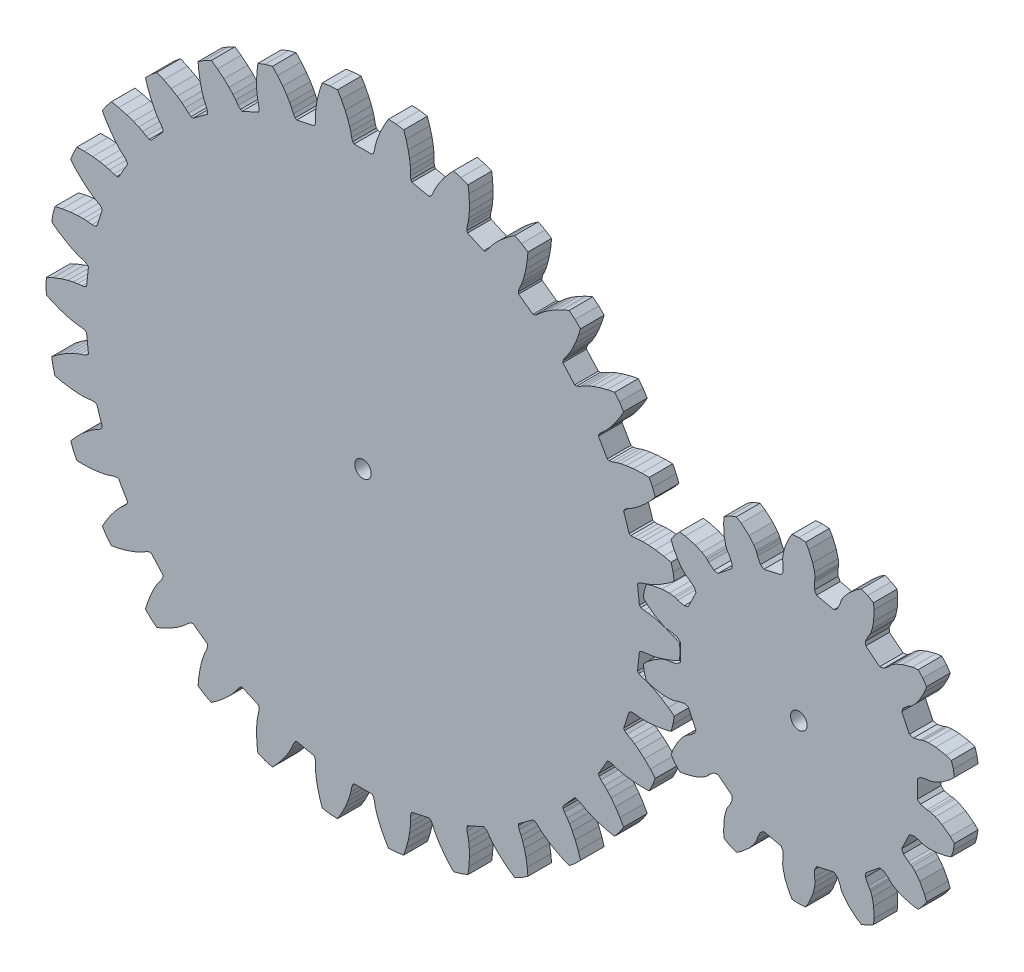
SolidWorks part; units mm, degrees
material "Corrugated Paper"
ref_plane "Front Plane" through (0, 0, 0) normal (0, 0, 1) x (1, 0, 0)
ref_plane "Top Plane" through (0, 0, 0) normal (0, 1, 0) x (1, 0, 0)
ref_plane "Right Plane" through (0, 0, 0) normal (1, 0, 0) x (0, 0, -1)
sketch "Model" plane through (0, 0, 0) normal (0, 0, 1) x (1, 0, 0)
  line L0 (40.3954, -9.6119) -> (40.6554, -8.6416)
  line L1 (40.6554, -8.6416) -> (40.8125, -7.6494)
  line L2 (40.8125, -7.6494) -> (40.0298, -7.0621)
  line L3 (40.0298, -7.0621) -> (39.103, -6.463)
  line L4 (39.103, -6.463) -> (38.2941, -6.0168)
  line L5 (38.2941, -6.0168) -> (37.6191, -5.7037)
  line L6 (37.6191, -5.7037) -> (37.0918, -5.5025)
  line L7 (37.0918, -5.5025) -> (36.5255, -5.3307)
  line L8 (36.5255, -5.3307) -> (36.1596, -5.1469)
  line L9 (36.1596, -5.1469) -> (35.9968, -4.9513)
  line L10 (35.9968, -4.9513) -> (36.2396, -2.6411)
  line L11 (36.2396, -2.6411) -> (36.4395, -2.4836)
  line L12 (36.4395, -2.4836) -> (36.8356, -2.3799)
  line L13 (36.8356, -2.3799) -> (37.4253, -2.3295)
  line L14 (37.4253, -2.3295) -> (37.9829, -2.2424)
  line L15 (37.9829, -2.2424) -> (38.7082, -2.0765)
  line L16 (38.7082, -2.0765) -> (39.5923, -1.8082)
  line L17 (39.5923, -1.8082) -> (40.6234, -1.4149)
  line L18 (40.6234, -1.4149) -> (41.5111, -1.0032)
  line L19 (41.5111, -1.0032) -> (41.5636, 0)
  line L20 (41.5636, 0) -> (41.5111, 1.0032)
  line L21 (41.5111, 1.0032) -> (40.6234, 1.4149)
  line L22 (40.6234, 1.4149) -> (39.5923, 1.8082)
  line L23 (39.5923, 1.8082) -> (38.7082, 2.0765)
  line L24 (38.7082, 2.0765) -> (37.9829, 2.2424)
  line L25 (37.9829, 2.2424) -> (37.4253, 2.3295)
  line L26 (37.4253, 2.3295) -> (36.8356, 2.3799)
  line L27 (36.8356, 2.3799) -> (36.4395, 2.4836)
  line L28 (36.4395, 2.4836) -> (36.2396, 2.6411)
  line L29 (36.2396, 2.6411) -> (35.9968, 4.9513)
  line L30 (35.9968, 4.9513) -> (36.1596, 5.1469)
  line L31 (36.1596, 5.1469) -> (36.5255, 5.3307)
  line L32 (36.5255, 5.3307) -> (37.0918, 5.5025)
  line L33 (37.0918, 5.5025) -> (37.6191, 5.7037)
  line L34 (37.6191, 5.7037) -> (38.2941, 6.0168)
  line L35 (38.2941, 6.0168) -> (39.103, 6.463)
  line L36 (39.103, 6.463) -> (40.0298, 7.0621)
  line L37 (40.0298, 7.0621) -> (40.8125, 7.6494)
  line L38 (40.8125, 7.6494) -> (40.6554, 8.6416)
  line L39 (40.6554, 8.6416) -> (40.3954, 9.6119)
  line L40 (40.3954, 9.6119) -> (39.4415, 9.83)
  line L41 (39.4415, 9.83) -> (38.3511, 10.0004)
  line L42 (38.3511, 10.0004) -> (37.4306, 10.079)
  line L43 (37.4306, 10.079) -> (36.6866, 10.0905)
  line L44 (36.6866, 10.0905) -> (36.1232, 10.0598)
  line L45 (36.1232, 10.0598) -> (35.5358, 9.9864)
  line L46 (35.5358, 9.9864) -> (35.1268, 10.0055)
  line L47 (35.1268, 10.0055) -> (34.8986, 10.118)
  line L48 (34.8986, 10.118) -> (34.1808, 12.3272)
  line L49 (34.1808, 12.3272) -> (34.2993, 12.5524)
  line L50 (34.2993, 12.5524) -> (34.619, 12.8082)
  line L51 (34.619, 12.8082) -> (35.1372, 13.0941)
  line L52 (35.1372, 13.0941) -> (35.6112, 13.4005)
  line L53 (35.6112, 13.4005) -> (36.2063, 13.8471)
  line L54 (36.2063, 13.8471) -> (36.9048, 14.4517)
  line L55 (36.9048, 14.4517) -> (37.6868, 15.2305)
  line L56 (37.6868, 15.2305) -> (38.3303, 15.9676)
  line L57 (38.3303, 15.9676) -> (37.9703, 16.9055)
  line L58 (37.9703, 16.9055) -> (37.5142, 17.8005)
  line L59 (37.5142, 17.8005) -> (36.5358, 17.8156)
  line L60 (36.5358, 17.8156) -> (35.4339, 17.7555)
  line L61 (35.4339, 17.7555) -> (34.5171, 17.641)
  line L62 (34.5171, 17.641) -> (33.787, 17.4976)
  line L63 (33.787, 17.4976) -> (33.2422, 17.3504)
  line L64 (33.2422, 17.3504) -> (32.683, 17.1565)
  line L65 (32.683, 17.1565) -> (32.279, 17.0901)
  line L66 (32.279, 17.0901) -> (32.0323, 17.1527)
  line L67 (32.0323, 17.1527) -> (30.8709, 19.1644)
  line L68 (30.8709, 19.1644) -> (30.94, 19.4093)
  line L69 (30.94, 19.4093) -> (31.1995, 19.726)
  line L70 (31.1995, 19.726) -> (31.647, 20.1134)
  line L71 (31.647, 20.1134) -> (32.0468, 20.5116)
  line L72 (32.0468, 20.5116) -> (32.5362, 21.0722)
  line L73 (32.5362, 21.0722) -> (33.0937, 21.8089)
  line L74 (33.0937, 21.8089) -> (33.6967, 22.7332)
  line L75 (33.6967, 22.7332) -> (34.1728, 23.588)
  line L76 (34.1728, 23.588) -> (33.6257, 24.4305)
  line L77 (33.6257, 24.4305) -> (32.9935, 25.2112)
  line L78 (32.9935, 25.2112) -> (32.0334, 25.0225)
  line L79 (32.0334, 25.0225) -> (30.968, 24.7346)
  line L80 (30.968, 24.7346) -> (30.0951, 24.4321)
  line L81 (30.0951, 24.4321) -> (29.4107, 24.1399)
  line L82 (29.4107, 24.1399) -> (28.9085, 23.8827)
  line L83 (28.9085, 23.8827) -> (28.4018, 23.5768)
  line L84 (28.4018, 23.5768) -> (28.0204, 23.4279)
  line L85 (28.0204, 23.4279) -> (27.7661, 23.4378)
  line L86 (27.7661, 23.4378) -> (26.2117, 25.1641)
  line L87 (26.2117, 25.1641) -> (26.2284, 25.418)
  line L88 (26.2284, 25.418) -> (26.4164, 25.7817)
  line L89 (26.4164, 25.7817) -> (26.7736, 26.2537)
  line L90 (26.7736, 26.2537) -> (27.0819, 26.7263)
  line L91 (27.0819, 26.7263) -> (27.444, 27.3764)
  line L92 (27.444, 27.3764) -> (27.8362, 28.2128)
  line L93 (27.8362, 28.2128) -> (28.2338, 29.2423)
  line L94 (28.2338, 29.2423) -> (28.5218, 30.1775)
  line L95 (28.5218, 30.1775) -> (27.8115, 30.8878)
  line L96 (27.8115, 30.8878) -> (27.0308, 31.52)
  line L97 (27.0308, 31.52) -> (26.1309, 31.1358)
  line L98 (26.1309, 31.1358) -> (25.1486, 30.6327)
  line L99 (25.1486, 30.6327) -> (24.3577, 30.1553)
  line L100 (24.3577, 30.1553) -> (23.7491, 29.7272)
  line L101 (23.7491, 29.7272) -> (23.3113, 29.3712)
  line L102 (23.3113, 29.3712) -> (22.8792, 28.9666)
  line L103 (22.8792, 28.9666) -> (22.5371, 28.7417)
  line L104 (22.5371, 28.7417) -> (22.2863, 28.6985)
  line L105 (22.2863, 28.6985) -> (20.407, 30.0639)
  line L106 (20.407, 30.0639) -> (20.3706, 30.3157)
  line L107 (20.3706, 30.3157) -> (20.4788, 30.7106)
  line L108 (20.4788, 30.7106) -> (20.7301, 31.2465)
  line L109 (20.7301, 31.2465) -> (20.9334, 31.7729)
  line L110 (20.9334, 31.7729) -> (21.1524, 32.4841)
  line L111 (21.1524, 32.4841) -> (21.3621, 33.3838)
  line L112 (21.3621, 33.3838) -> (21.537, 34.4735)
  line L113 (21.537, 34.4735) -> (21.6243, 35.448)
  line L114 (21.6243, 35.448) -> (20.7818, 35.9952)
  line L115 (20.7818, 35.9952) -> (19.8868, 36.4512)
  line L116 (19.8868, 36.4512) -> (19.0864, 35.8883)
  line L117 (19.0864, 35.8883) -> (18.2302, 35.192)
  line L118 (18.2302, 35.192) -> (17.5558, 34.5606)
  line L119 (17.5558, 34.5606) -> (17.0495, 34.0153)
  line L120 (17.0495, 34.0153) -> (16.6952, 33.5761)
  line L121 (16.6952, 33.5761) -> (16.3568, 33.0905)
  line L122 (16.3568, 33.0905) -> (16.0689, 32.7993)
  line L123 (16.0689, 32.7993) -> (15.8326, 32.705)
  line L124 (15.8326, 32.705) -> (13.7105, 33.6498)
  line L125 (13.7105, 33.6498) -> (13.6225, 33.8886)
  line L126 (13.6225, 33.8886) -> (13.6462, 34.2973)
  line L127 (13.6462, 34.2973) -> (13.7806, 34.8737)
  line L128 (13.7806, 34.8737) -> (13.87, 35.4309)
  line L129 (13.87, 35.4309) -> (13.9364, 36.172)
  line L130 (13.9364, 36.172) -> (13.9544, 37.0957)
  line L131 (13.9544, 37.0957) -> (13.8989, 38.1979)
  line L132 (13.8989, 38.1979) -> (13.7817, 39.1694)
  line L133 (13.7817, 39.1694) -> (12.8439, 39.5294)
  line L134 (12.8439, 39.5294) -> (11.8736, 39.7894)
  line L135 (11.8736, 39.7894) -> (11.2077, 39.0724)
  line L136 (11.2077, 39.0724) -> (10.515, 38.2133)
  line L137 (10.515, 38.2133) -> (9.9866, 37.4554)
  line L138 (9.9866, 37.4554) -> (9.6047, 36.8168)
  line L139 (9.6047, 36.8168) -> (9.3496, 36.3135)
  line L140 (9.3496, 36.3135) -> (9.1194, 35.7682)
  line L141 (9.1194, 35.7682) -> (8.8984, 35.4235)
  line L142 (8.8984, 35.4235) -> (8.6869, 35.2821)
  line L143 (8.6869, 35.2821) -> (6.4147, 35.765)
  line L144 (6.4147, 35.765) -> (6.2789, 35.9803)
  line L145 (6.2789, 35.9803) -> (6.2172, 36.385)
  line L146 (6.2172, 36.385) -> (6.2288, 36.9768)
  line L147 (6.2288, 36.9768) -> (6.2004, 37.5404)
  line L148 (6.2004, 37.5404) -> (6.1113, 38.2791)
  line L149 (6.1113, 38.2791) -> (5.9368, 39.1864)
  line L150 (5.9368, 39.1864) -> (5.6534, 40.253)
  line L151 (5.6534, 40.253) -> (5.3368, 41.1788)
  line L152 (5.3368, 41.1788) -> (4.3446, 41.3359)
  line L153 (4.3446, 41.3359) -> (3.3414, 41.3885)
  line L154 (3.3414, 41.3885) -> (2.8392, 40.5488)
  line L155 (2.8392, 40.5488) -> (2.3402, 39.5644)
  line L156 (2.3402, 39.5644) -> (1.981, 38.7132)
  line L157 (1.981, 38.7132) -> (1.7402, 38.0092)
  line L158 (1.7402, 38.0092) -> (1.5952, 37.4638)
  line L159 (1.5952, 37.4638) -> (1.4835, 36.8826)
  line L160 (1.4835, 36.8826) -> (1.339, 36.4995)
  line L161 (1.339, 36.4995) -> (1.1615, 36.3172)
  line L162 (1.1615, 36.3172) -> (-1.1615, 36.3172)
  line L163 (-1.1615, 36.3172) -> (-1.339, 36.4995)
  line L164 (-1.339, 36.4995) -> (-1.4835, 36.8826)
  line L165 (-1.4835, 36.8826) -> (-1.5952, 37.4638)
  line L166 (-1.5952, 37.4638) -> (-1.7402, 38.0092)
  line L167 (-1.7402, 38.0092) -> (-1.981, 38.7132)
  line L168 (-1.981, 38.7132) -> (-2.3402, 39.5644)
  line L169 (-2.3402, 39.5644) -> (-2.8392, 40.5488)
  line L170 (-2.8392, 40.5488) -> (-3.3414, 41.3885)
  line L171 (-3.3414, 41.3885) -> (-4.3446, 41.3359)
  line L172 (-4.3446, 41.3359) -> (-5.3368, 41.1788)
  line L173 (-5.3368, 41.1788) -> (-5.6534, 40.253)
  line L174 (-5.6534, 40.253) -> (-5.9368, 39.1864)
  line L175 (-5.9368, 39.1864) -> (-6.1113, 38.2791)
  line L176 (-6.1113, 38.2791) -> (-6.2004, 37.5404)
  line L177 (-6.2004, 37.5404) -> (-6.2288, 36.9768)
  line L178 (-6.2288, 36.9768) -> (-6.2172, 36.385)
  line L179 (-6.2172, 36.385) -> (-6.2789, 35.9803)
  line L180 (-6.2789, 35.9803) -> (-6.4147, 35.765)
  line L181 (-6.4147, 35.765) -> (-8.6869, 35.2821)
  line L182 (-8.6869, 35.2821) -> (-8.8984, 35.4235)
  line L183 (-8.8984, 35.4235) -> (-9.1194, 35.7682)
  line L184 (-9.1194, 35.7682) -> (-9.3496, 36.3135)
  line L185 (-9.3496, 36.3135) -> (-9.6047, 36.8168)
  line L186 (-9.6047, 36.8168) -> (-9.9866, 37.4554)
  line L187 (-9.9866, 37.4554) -> (-10.515, 38.2133)
  line L188 (-10.515, 38.2133) -> (-11.2077, 39.0724)
  line L189 (-11.2077, 39.0724) -> (-11.8736, 39.7894)
  line L190 (-11.8736, 39.7894) -> (-12.8439, 39.5294)
  line L191 (-12.8439, 39.5294) -> (-13.7817, 39.1694)
  line L192 (-13.7817, 39.1694) -> (-13.8989, 38.1979)
  line L193 (-13.8989, 38.1979) -> (-13.9544, 37.0957)
  line L194 (-13.9544, 37.0957) -> (-13.9364, 36.172)
  line L195 (-13.9364, 36.172) -> (-13.87, 35.4309)
  line L196 (-13.87, 35.4309) -> (-13.7806, 34.8737)
  line L197 (-13.7806, 34.8737) -> (-13.6462, 34.2973)
  line L198 (-13.6462, 34.2973) -> (-13.6225, 33.8886)
  line L199 (-13.6225, 33.8886) -> (-13.7105, 33.6498)
  line L200 (-13.7105, 33.6498) -> (-15.8326, 32.705)
  line L201 (-15.8326, 32.705) -> (-16.0689, 32.7993)
  line L202 (-16.0689, 32.7993) -> (-16.3568, 33.0905)
  line L203 (-16.3568, 33.0905) -> (-16.6952, 33.5761)
  line L204 (-16.6952, 33.5761) -> (-17.0495, 34.0153)
  line L205 (-17.0495, 34.0153) -> (-17.5558, 34.5606)
  line L206 (-17.5558, 34.5606) -> (-18.2302, 35.192)
  line L207 (-18.2302, 35.192) -> (-19.0864, 35.8883)
  line L208 (-19.0864, 35.8883) -> (-19.8868, 36.4512)
  line L209 (-19.8868, 36.4512) -> (-20.7818, 35.9952)
  line L210 (-20.7818, 35.9952) -> (-21.6243, 35.448)
  line L211 (-21.6243, 35.448) -> (-21.537, 34.4735)
  line L212 (-21.537, 34.4735) -> (-21.3621, 33.3838)
  line L213 (-21.3621, 33.3838) -> (-21.1524, 32.4841)
  line L214 (-21.1524, 32.4841) -> (-20.9334, 31.7729)
  line L215 (-20.9334, 31.7729) -> (-20.7301, 31.2465)
  line L216 (-20.7301, 31.2465) -> (-20.4788, 30.7106)
  line L217 (-20.4788, 30.7106) -> (-20.3706, 30.3157)
  line L218 (-20.3706, 30.3157) -> (-20.407, 30.0639)
  line L219 (-20.407, 30.0639) -> (-22.2863, 28.6985)
  line L220 (-22.2863, 28.6985) -> (-22.5371, 28.7417)
  line L221 (-22.5371, 28.7417) -> (-22.8792, 28.9666)
  line L222 (-22.8792, 28.9666) -> (-23.3113, 29.3712)
  line L223 (-23.3113, 29.3712) -> (-23.7491, 29.7272)
  line L224 (-23.7491, 29.7272) -> (-24.3577, 30.1553)
  line L225 (-24.3577, 30.1553) -> (-25.1486, 30.6327)
  line L226 (-25.1486, 30.6327) -> (-26.1309, 31.1358)
  line L227 (-26.1309, 31.1358) -> (-27.0308, 31.52)
  line L228 (-27.0308, 31.52) -> (-27.8115, 30.8878)
  line L229 (-27.8115, 30.8878) -> (-28.5218, 30.1775)
  line L230 (-28.5218, 30.1775) -> (-28.2338, 29.2423)
  line L231 (-28.2338, 29.2423) -> (-27.8362, 28.2128)
  line L232 (-27.8362, 28.2128) -> (-27.444, 27.3764)
  line L233 (-27.444, 27.3764) -> (-27.0819, 26.7263)
  line L234 (-27.0819, 26.7263) -> (-26.7736, 26.2537)
  line L235 (-26.7736, 26.2537) -> (-26.4164, 25.7817)
  line L236 (-26.4164, 25.7817) -> (-26.2284, 25.418)
  line L237 (-26.2284, 25.418) -> (-26.2117, 25.1641)
  line L238 (-26.2117, 25.1641) -> (-27.7661, 23.4378)
  line L239 (-27.7661, 23.4378) -> (-28.0204, 23.4279)
  line L240 (-28.0204, 23.4279) -> (-28.4018, 23.5768)
  line L241 (-28.4018, 23.5768) -> (-28.9085, 23.8827)
  line L242 (-28.9085, 23.8827) -> (-29.4107, 24.1399)
  line L243 (-29.4107, 24.1399) -> (-30.0951, 24.4321)
  line L244 (-30.0951, 24.4321) -> (-30.968, 24.7346)
  line L245 (-30.968, 24.7346) -> (-32.0334, 25.0225)
  line L246 (-32.0334, 25.0225) -> (-32.9935, 25.2112)
  line L247 (-32.9935, 25.2112) -> (-33.6257, 24.4305)
  line L248 (-33.6257, 24.4305) -> (-34.1728, 23.588)
  line L249 (-34.1728, 23.588) -> (-33.6967, 22.7332)
  line L250 (-33.6967, 22.7332) -> (-33.0937, 21.8089)
  line L251 (-33.0937, 21.8089) -> (-32.5362, 21.0722)
  line L252 (-32.5362, 21.0722) -> (-32.0468, 20.5116)
  line L253 (-32.0468, 20.5116) -> (-31.647, 20.1134)
  line L254 (-31.647, 20.1134) -> (-31.1995, 19.726)
  line L255 (-31.1995, 19.726) -> (-30.94, 19.4093)
  line L256 (-30.94, 19.4093) -> (-30.8709, 19.1644)
  line L257 (-30.8709, 19.1644) -> (-32.0323, 17.1527)
  line L258 (-32.0323, 17.1527) -> (-32.279, 17.0901)
  line L259 (-32.279, 17.0901) -> (-32.683, 17.1565)
  line L260 (-32.683, 17.1565) -> (-33.2422, 17.3504)
  line L261 (-33.2422, 17.3504) -> (-33.787, 17.4976)
  line L262 (-33.787, 17.4976) -> (-34.5171, 17.641)
  line L263 (-34.5171, 17.641) -> (-35.4339, 17.7555)
  line L264 (-35.4339, 17.7555) -> (-36.5358, 17.8156)
  line L265 (-36.5358, 17.8156) -> (-37.5142, 17.8005)
  line L266 (-37.5142, 17.8005) -> (-37.9703, 16.9055)
  line L267 (-37.9703, 16.9055) -> (-38.3303, 15.9676)
  line L268 (-38.3303, 15.9676) -> (-37.6868, 15.2305)
  line L269 (-37.6868, 15.2305) -> (-36.9048, 14.4517)
  line L270 (-36.9048, 14.4517) -> (-36.2063, 13.8471)
  line L271 (-36.2063, 13.8471) -> (-35.6112, 13.4005)
  line L272 (-35.6112, 13.4005) -> (-35.1372, 13.0941)
  line L273 (-35.1372, 13.0941) -> (-34.619, 12.8082)
  line L274 (-34.619, 12.8082) -> (-34.2993, 12.5524)
  line L275 (-34.2993, 12.5524) -> (-34.1808, 12.3272)
  line L276 (-34.1808, 12.3272) -> (-34.8986, 10.118)
  line L277 (-34.8986, 10.118) -> (-35.1268, 10.0055)
  line L278 (-35.1268, 10.0055) -> (-35.5358, 9.9864)
  line L279 (-35.5358, 9.9864) -> (-36.1232, 10.0598)
  line L280 (-36.1232, 10.0598) -> (-36.6866, 10.0905)
  line L281 (-36.6866, 10.0905) -> (-37.4306, 10.079)
  line L282 (-37.4306, 10.079) -> (-38.3511, 10.0004)
  line L283 (-38.3511, 10.0004) -> (-39.4415, 9.83)
  line L284 (-39.4415, 9.83) -> (-40.3954, 9.6119)
  line L285 (-40.3954, 9.6119) -> (-40.6554, 8.6416)
  line L286 (-40.6554, 8.6416) -> (-40.8125, 7.6494)
  line L287 (-40.8125, 7.6494) -> (-40.0298, 7.0621)
  line L288 (-40.0298, 7.0621) -> (-39.103, 6.463)
  line L289 (-39.103, 6.463) -> (-38.2941, 6.0168)
  line L290 (-38.2941, 6.0168) -> (-37.6191, 5.7037)
  line L291 (-37.6191, 5.7037) -> (-37.0918, 5.5025)
  line L292 (-37.0918, 5.5025) -> (-36.5255, 5.3307)
  line L293 (-36.5255, 5.3307) -> (-36.1596, 5.1469)
  line L294 (-36.1596, 5.1469) -> (-35.9968, 4.9513)
  line L295 (-35.9968, 4.9513) -> (-36.2396, 2.6411)
  line L296 (-36.2396, 2.6411) -> (-36.4395, 2.4836)
  line L297 (-36.4395, 2.4836) -> (-36.8356, 2.3799)
  line L298 (-36.8356, 2.3799) -> (-37.4253, 2.3295)
  line L299 (-37.4253, 2.3295) -> (-37.9829, 2.2424)
  line L300 (-37.9829, 2.2424) -> (-38.7082, 2.0765)
  line L301 (-38.7082, 2.0765) -> (-39.5923, 1.8082)
  line L302 (-39.5923, 1.8082) -> (-40.6234, 1.4149)
  line L303 (-40.6234, 1.4149) -> (-41.5111, 1.0032)
  line L304 (-41.5111, 1.0032) -> (-41.5636, 0)
  line L305 (-41.5636, 0) -> (-41.5111, -1.0032)
  line L306 (-41.5111, -1.0032) -> (-40.6234, -1.4149)
  line L307 (-40.6234, -1.4149) -> (-39.5923, -1.8082)
  line L308 (-39.5923, -1.8082) -> (-38.7082, -2.0765)
  line L309 (-38.7082, -2.0765) -> (-37.9829, -2.2424)
  line L310 (-37.9829, -2.2424) -> (-37.4253, -2.3295)
  line L311 (-37.4253, -2.3295) -> (-36.8356, -2.3799)
  line L312 (-36.8356, -2.3799) -> (-36.4395, -2.4836)
  line L313 (-36.4395, -2.4836) -> (-36.2396, -2.6411)
  line L314 (-36.2396, -2.6411) -> (-35.9968, -4.9513)
  line L315 (-35.9968, -4.9513) -> (-36.1596, -5.1469)
  line L316 (-36.1596, -5.1469) -> (-36.5255, -5.3307)
  line L317 (-36.5255, -5.3307) -> (-37.0918, -5.5025)
  line L318 (-37.0918, -5.5025) -> (-37.6191, -5.7037)
  line L319 (-37.6191, -5.7037) -> (-38.2941, -6.0168)
  line L320 (-38.2941, -6.0168) -> (-39.103, -6.463)
  line L321 (-39.103, -6.463) -> (-40.0298, -7.0621)
  line L322 (-40.0298, -7.0621) -> (-40.8125, -7.6494)
  line L323 (-40.8125, -7.6494) -> (-40.6554, -8.6416)
  line L324 (-40.6554, -8.6416) -> (-40.3954, -9.6119)
  line L325 (-40.3954, -9.6119) -> (-39.4415, -9.83)
  line L326 (-39.4415, -9.83) -> (-38.3511, -10.0004)
  line L327 (-38.3511, -10.0004) -> (-37.4306, -10.079)
  line L328 (-37.4306, -10.079) -> (-36.6866, -10.0905)
  line L329 (-36.6866, -10.0905) -> (-36.1232, -10.0598)
  line L330 (-36.1232, -10.0598) -> (-35.5358, -9.9864)
  line L331 (-35.5358, -9.9864) -> (-35.1268, -10.0055)
  line L332 (-35.1268, -10.0055) -> (-34.8986, -10.118)
  line L333 (-34.8986, -10.118) -> (-34.1808, -12.3272)
  line L334 (-34.1808, -12.3272) -> (-34.2993, -12.5524)
  line L335 (-34.2993, -12.5524) -> (-34.619, -12.8082)
  line L336 (-34.619, -12.8082) -> (-35.1372, -13.0941)
  line L337 (-35.1372, -13.0941) -> (-35.6112, -13.4005)
  line L338 (-35.6112, -13.4005) -> (-36.2063, -13.8471)
  line L339 (-36.2063, -13.8471) -> (-36.9048, -14.4517)
  line L340 (-36.9048, -14.4517) -> (-37.6868, -15.2305)
  line L341 (-37.6868, -15.2305) -> (-38.3303, -15.9676)
  line L342 (-38.3303, -15.9676) -> (-37.9703, -16.9055)
  line L343 (-37.9703, -16.9055) -> (-37.5142, -17.8005)
  line L344 (-37.5142, -17.8005) -> (-36.5358, -17.8156)
  line L345 (-36.5358, -17.8156) -> (-35.4339, -17.7555)
  line L346 (-35.4339, -17.7555) -> (-34.5171, -17.641)
  line L347 (-34.5171, -17.641) -> (-33.787, -17.4976)
  line L348 (-33.787, -17.4976) -> (-33.2422, -17.3504)
  line L349 (-33.2422, -17.3504) -> (-32.683, -17.1565)
  line L350 (-32.683, -17.1565) -> (-32.279, -17.0901)
  line L351 (-32.279, -17.0901) -> (-32.0323, -17.1527)
  line L352 (-32.0323, -17.1527) -> (-30.8709, -19.1644)
  line L353 (-30.8709, -19.1644) -> (-30.94, -19.4093)
  line L354 (-30.94, -19.4093) -> (-31.1995, -19.726)
  line L355 (-31.1995, -19.726) -> (-31.647, -20.1134)
  line L356 (-31.647, -20.1134) -> (-32.0468, -20.5116)
  line L357 (-32.0468, -20.5116) -> (-32.5362, -21.0722)
  line L358 (-32.5362, -21.0722) -> (-33.0937, -21.8089)
  line L359 (-33.0937, -21.8089) -> (-33.6967, -22.7332)
  line L360 (-33.6967, -22.7332) -> (-34.1728, -23.588)
  line L361 (-34.1728, -23.588) -> (-33.6257, -24.4305)
  line L362 (-33.6257, -24.4305) -> (-32.9935, -25.2112)
  line L363 (-32.9935, -25.2112) -> (-32.0334, -25.0225)
  line L364 (-32.0334, -25.0225) -> (-30.968, -24.7346)
  line L365 (-30.968, -24.7346) -> (-30.0951, -24.4321)
  line L366 (-30.0951, -24.4321) -> (-29.4107, -24.1399)
  line L367 (-29.4107, -24.1399) -> (-28.9085, -23.8827)
  line L368 (-28.9085, -23.8827) -> (-28.4018, -23.5768)
  line L369 (-28.4018, -23.5768) -> (-28.0204, -23.4279)
  line L370 (-28.0204, -23.4279) -> (-27.7661, -23.4378)
  line L371 (-27.7661, -23.4378) -> (-26.2117, -25.1641)
  line L372 (-26.2117, -25.1641) -> (-26.2284, -25.418)
  line L373 (-26.2284, -25.418) -> (-26.4164, -25.7817)
  line L374 (-26.4164, -25.7817) -> (-26.7736, -26.2537)
  line L375 (-26.7736, -26.2537) -> (-27.0819, -26.7263)
  line L376 (-27.0819, -26.7263) -> (-27.444, -27.3764)
  line L377 (-27.444, -27.3764) -> (-27.8362, -28.2128)
  line L378 (-27.8362, -28.2128) -> (-28.2338, -29.2423)
  line L379 (-28.2338, -29.2423) -> (-28.5218, -30.1775)
  line L380 (-28.5218, -30.1775) -> (-27.8115, -30.8878)
  line L381 (-27.8115, -30.8878) -> (-27.0308, -31.52)
  line L382 (-27.0308, -31.52) -> (-26.1309, -31.1358)
  line L383 (-26.1309, -31.1358) -> (-25.1486, -30.6327)
  line L384 (-25.1486, -30.6327) -> (-24.3577, -30.1553)
  line L385 (-24.3577, -30.1553) -> (-23.7491, -29.7272)
  line L386 (-23.7491, -29.7272) -> (-23.3113, -29.3712)
  line L387 (-23.3113, -29.3712) -> (-22.8792, -28.9666)
  line L388 (-22.8792, -28.9666) -> (-22.5371, -28.7417)
  line L389 (-22.5371, -28.7417) -> (-22.2863, -28.6985)
  line L390 (-22.2863, -28.6985) -> (-20.407, -30.0639)
  line L391 (-20.407, -30.0639) -> (-20.3706, -30.3157)
  line L392 (-20.3706, -30.3157) -> (-20.4788, -30.7106)
  line L393 (-20.4788, -30.7106) -> (-20.7301, -31.2465)
  line L394 (-20.7301, -31.2465) -> (-20.9334, -31.7729)
  line L395 (-20.9334, -31.7729) -> (-21.1524, -32.4841)
  line L396 (-21.1524, -32.4841) -> (-21.3621, -33.3838)
  line L397 (-21.3621, -33.3838) -> (-21.537, -34.4735)
  line L398 (-21.537, -34.4735) -> (-21.6243, -35.448)
  line L399 (-21.6243, -35.448) -> (-20.7818, -35.9952)
  line L400 (-20.7818, -35.9952) -> (-19.8868, -36.4512)
  line L401 (-19.8868, -36.4512) -> (-19.0864, -35.8883)
  line L402 (-19.0864, -35.8883) -> (-18.2302, -35.192)
  line L403 (-18.2302, -35.192) -> (-17.5558, -34.5606)
  line L404 (-17.5558, -34.5606) -> (-17.0495, -34.0153)
  line L405 (-17.0495, -34.0153) -> (-16.6952, -33.5761)
  line L406 (-16.6952, -33.5761) -> (-16.3568, -33.0905)
  line L407 (-16.3568, -33.0905) -> (-16.0689, -32.7993)
  line L408 (-16.0689, -32.7993) -> (-15.8326, -32.705)
  line L409 (-15.8326, -32.705) -> (-13.7105, -33.6498)
  line L410 (-13.7105, -33.6498) -> (-13.6225, -33.8886)
  line L411 (-13.6225, -33.8886) -> (-13.6462, -34.2973)
  line L412 (-13.6462, -34.2973) -> (-13.7806, -34.8737)
  line L413 (-13.7806, -34.8737) -> (-13.87, -35.4309)
  line L414 (-13.87, -35.4309) -> (-13.9364, -36.172)
  line L415 (-13.9364, -36.172) -> (-13.9544, -37.0957)
  line L416 (-13.9544, -37.0957) -> (-13.8989, -38.1979)
  line L417 (-13.8989, -38.1979) -> (-13.7817, -39.1694)
  line L418 (-13.7817, -39.1694) -> (-12.8439, -39.5294)
  line L419 (-12.8439, -39.5294) -> (-11.8736, -39.7894)
  line L420 (-11.8736, -39.7894) -> (-11.2077, -39.0724)
  line L421 (-11.2077, -39.0724) -> (-10.515, -38.2133)
  line L422 (-10.515, -38.2133) -> (-9.9866, -37.4554)
  line L423 (-9.9866, -37.4554) -> (-9.6047, -36.8168)
  line L424 (-9.6047, -36.8168) -> (-9.3496, -36.3135)
  line L425 (-9.3496, -36.3135) -> (-9.1194, -35.7682)
  line L426 (-9.1194, -35.7682) -> (-8.8984, -35.4235)
  line L427 (-8.8984, -35.4235) -> (-8.6869, -35.2821)
  line L428 (-8.6869, -35.2821) -> (-6.4147, -35.765)
  line L429 (-6.4147, -35.765) -> (-6.2789, -35.9803)
  line L430 (-6.2789, -35.9803) -> (-6.2172, -36.385)
  line L431 (-6.2172, -36.385) -> (-6.2288, -36.9768)
  line L432 (-6.2288, -36.9768) -> (-6.2004, -37.5404)
  line L433 (-6.2004, -37.5404) -> (-6.1113, -38.2791)
  line L434 (-6.1113, -38.2791) -> (-5.9368, -39.1864)
  line L435 (-5.9368, -39.1864) -> (-5.6534, -40.253)
  line L436 (-5.6534, -40.253) -> (-5.3368, -41.1788)
  line L437 (-5.3368, -41.1788) -> (-4.3446, -41.3359)
  line L438 (-4.3446, -41.3359) -> (-3.3414, -41.3885)
  line L439 (-3.3414, -41.3885) -> (-2.8392, -40.5488)
  line L440 (-2.8392, -40.5488) -> (-2.3402, -39.5644)
  line L441 (-2.3402, -39.5644) -> (-1.981, -38.7132)
  line L442 (-1.981, -38.7132) -> (-1.7402, -38.0092)
  line L443 (-1.7402, -38.0092) -> (-1.5952, -37.4638)
  line L444 (-1.5952, -37.4638) -> (-1.4835, -36.8826)
  line L445 (-1.4835, -36.8826) -> (-1.339, -36.4995)
  line L446 (-1.339, -36.4995) -> (-1.1615, -36.3172)
  line L447 (-1.1615, -36.3172) -> (1.1615, -36.3172)
  line L448 (1.1615, -36.3172) -> (1.339, -36.4995)
  line L449 (1.339, -36.4995) -> (1.4835, -36.8826)
  line L450 (1.4835, -36.8826) -> (1.5952, -37.4638)
  line L451 (1.5952, -37.4638) -> (1.7402, -38.0092)
  line L452 (1.7402, -38.0092) -> (1.981, -38.7132)
  line L453 (1.981, -38.7132) -> (2.3402, -39.5644)
  line L454 (2.3402, -39.5644) -> (2.8392, -40.5488)
  line L455 (2.8392, -40.5488) -> (3.3414, -41.3885)
  line L456 (3.3414, -41.3885) -> (4.3446, -41.3359)
  line L457 (4.3446, -41.3359) -> (5.3368, -41.1788)
  line L458 (5.3368, -41.1788) -> (5.6534, -40.253)
  line L459 (5.6534, -40.253) -> (5.9368, -39.1864)
  line L460 (5.9368, -39.1864) -> (6.1113, -38.2791)
  line L461 (6.1113, -38.2791) -> (6.2004, -37.5404)
  line L462 (6.2004, -37.5404) -> (6.2288, -36.9768)
  line L463 (6.2288, -36.9768) -> (6.2172, -36.385)
  line L464 (6.2172, -36.385) -> (6.2789, -35.9803)
  line L465 (6.2789, -35.9803) -> (6.4147, -35.765)
  line L466 (6.4147, -35.765) -> (8.6869, -35.2821)
  line L467 (8.6869, -35.2821) -> (8.8984, -35.4235)
  line L468 (8.8984, -35.4235) -> (9.1194, -35.7682)
  line L469 (9.1194, -35.7682) -> (9.3496, -36.3135)
  line L470 (9.3496, -36.3135) -> (9.6047, -36.8168)
  line L471 (9.6047, -36.8168) -> (9.9866, -37.4554)
  line L472 (9.9866, -37.4554) -> (10.515, -38.2133)
  line L473 (10.515, -38.2133) -> (11.2077, -39.0724)
  line L474 (11.2077, -39.0724) -> (11.8736, -39.7894)
  line L475 (11.8736, -39.7894) -> (12.8439, -39.5294)
  line L476 (12.8439, -39.5294) -> (13.7817, -39.1694)
  line L477 (13.7817, -39.1694) -> (13.8989, -38.1979)
  line L478 (13.8989, -38.1979) -> (13.9544, -37.0957)
  line L479 (13.9544, -37.0957) -> (13.9364, -36.172)
  line L480 (13.9364, -36.172) -> (13.87, -35.4309)
  line L481 (13.87, -35.4309) -> (13.7806, -34.8737)
  line L482 (13.7806, -34.8737) -> (13.6462, -34.2973)
  line L483 (13.6462, -34.2973) -> (13.6225, -33.8886)
  line L484 (13.6225, -33.8886) -> (13.7105, -33.6498)
  line L485 (13.7105, -33.6498) -> (15.8326, -32.705)
  line L486 (15.8326, -32.705) -> (16.0689, -32.7993)
  line L487 (16.0689, -32.7993) -> (16.3568, -33.0905)
  line L488 (16.3568, -33.0905) -> (16.6952, -33.5761)
  line L489 (16.6952, -33.5761) -> (17.0495, -34.0153)
  line L490 (17.0495, -34.0153) -> (17.5558, -34.5606)
  line L491 (17.5558, -34.5606) -> (18.2302, -35.192)
  line L492 (18.2302, -35.192) -> (19.0864, -35.8883)
  line L493 (19.0864, -35.8883) -> (19.8868, -36.4512)
  line L494 (19.8868, -36.4512) -> (20.7818, -35.9952)
  line L495 (20.7818, -35.9952) -> (21.6243, -35.448)
  line L496 (21.6243, -35.448) -> (21.537, -34.4735)
  line L497 (21.537, -34.4735) -> (21.3621, -33.3838)
  line L498 (21.3621, -33.3838) -> (21.1524, -32.4841)
  line L499 (21.1524, -32.4841) -> (20.9334, -31.7729)
  line L500 (20.9334, -31.7729) -> (20.7301, -31.2465)
  line L501 (20.7301, -31.2465) -> (20.4788, -30.7106)
  line L502 (20.4788, -30.7106) -> (20.3706, -30.3157)
  line L503 (20.3706, -30.3157) -> (20.407, -30.0639)
  line L504 (20.407, -30.0639) -> (22.2863, -28.6985)
  line L505 (22.2863, -28.6985) -> (22.5371, -28.7417)
  line L506 (22.5371, -28.7417) -> (22.8792, -28.9666)
  line L507 (22.8792, -28.9666) -> (23.3113, -29.3712)
  line L508 (23.3113, -29.3712) -> (23.7491, -29.7272)
  line L509 (23.7491, -29.7272) -> (24.3577, -30.1553)
  line L510 (24.3577, -30.1553) -> (25.1486, -30.6327)
  line L511 (25.1486, -30.6327) -> (26.1309, -31.1358)
  line L512 (26.1309, -31.1358) -> (27.0308, -31.52)
  line L513 (27.0308, -31.52) -> (27.8115, -30.8878)
  line L514 (27.8115, -30.8878) -> (28.5218, -30.1775)
  line L515 (28.5218, -30.1775) -> (28.2338, -29.2423)
  line L516 (28.2338, -29.2423) -> (27.8362, -28.2128)
  line L517 (27.8362, -28.2128) -> (27.444, -27.3764)
  line L518 (27.444, -27.3764) -> (27.0819, -26.7263)
  line L519 (27.0819, -26.7263) -> (26.7736, -26.2537)
  line L520 (26.7736, -26.2537) -> (26.4164, -25.7817)
  line L521 (26.4164, -25.7817) -> (26.2284, -25.418)
  line L522 (26.2284, -25.418) -> (26.2117, -25.1641)
  line L523 (26.2117, -25.1641) -> (27.7661, -23.4378)
  line L524 (27.7661, -23.4378) -> (28.0204, -23.4279)
  line L525 (28.0204, -23.4279) -> (28.4018, -23.5768)
  line L526 (28.4018, -23.5768) -> (28.9085, -23.8827)
  line L527 (28.9085, -23.8827) -> (29.4107, -24.1399)
  line L528 (29.4107, -24.1399) -> (30.0951, -24.4321)
  line L529 (30.0951, -24.4321) -> (30.968, -24.7346)
  line L530 (30.968, -24.7346) -> (32.0334, -25.0225)
  line L531 (32.0334, -25.0225) -> (32.9935, -25.2112)
  line L532 (32.9935, -25.2112) -> (33.6257, -24.4305)
  line L533 (33.6257, -24.4305) -> (34.1728, -23.588)
  line L534 (34.1728, -23.588) -> (33.6967, -22.7332)
  line L535 (33.6967, -22.7332) -> (33.0937, -21.8089)
  line L536 (33.0937, -21.8089) -> (32.5362, -21.0722)
  line L537 (32.5362, -21.0722) -> (32.0468, -20.5116)
  line L538 (32.0468, -20.5116) -> (31.647, -20.1134)
  line L539 (31.647, -20.1134) -> (31.1995, -19.726)
  line L540 (31.1995, -19.726) -> (30.94, -19.4093)
  line L541 (30.94, -19.4093) -> (30.8709, -19.1644)
  line L542 (30.8709, -19.1644) -> (32.0323, -17.1527)
  line L543 (32.0323, -17.1527) -> (32.279, -17.0901)
  line L544 (32.279, -17.0901) -> (32.683, -17.1565)
  line L545 (32.683, -17.1565) -> (33.2422, -17.3504)
  line L546 (33.2422, -17.3504) -> (33.787, -17.4976)
  line L547 (33.787, -17.4976) -> (34.5171, -17.641)
  line L548 (34.5171, -17.641) -> (35.4339, -17.7555)
  line L549 (35.4339, -17.7555) -> (36.5358, -17.8156)
  line L550 (36.5358, -17.8156) -> (37.5142, -17.8005)
  line L551 (37.5142, -17.8005) -> (37.9703, -16.9055)
  line L552 (37.9703, -16.9055) -> (38.3303, -15.9676)
  line L553 (38.3303, -15.9676) -> (37.6868, -15.2305)
  line L554 (37.6868, -15.2305) -> (36.9048, -14.4517)
  line L555 (36.9048, -14.4517) -> (36.2063, -13.8471)
  line L556 (36.2063, -13.8471) -> (35.6112, -13.4005)
  line L557 (35.6112, -13.4005) -> (35.1372, -13.0941)
  line L558 (35.1372, -13.0941) -> (34.619, -12.8082)
  line L559 (34.619, -12.8082) -> (34.2993, -12.5524)
  line L560 (34.2993, -12.5524) -> (34.1808, -12.3272)
  line L561 (34.1808, -12.3272) -> (34.8986, -10.118)
  line L562 (34.8986, -10.118) -> (35.1268, -10.0055)
  line L563 (35.1268, -10.0055) -> (35.5358, -9.9864)
  line L564 (35.5358, -9.9864) -> (36.1232, -10.0598)
  line L565 (36.1232, -10.0598) -> (36.6866, -10.0905)
  line L566 (36.6866, -10.0905) -> (37.4306, -10.079)
  line L567 (37.4306, -10.079) -> (38.3511, -10.0004)
  line L568 (38.3511, -10.0004) -> (39.4415, -9.83)
  line L569 (39.4415, -9.83) -> (40.3954, -9.6119)
  line L570 (37.1509, 5.4729) -> (36.8892, 4.6244)
  line L571 (36.8892, 4.6244) -> (36.7569, 3.7464)
  line L572 (36.7569, 3.7464) -> (37.2945, 3.2164)
  line L573 (37.2945, 3.2164) -> (38.3947, 2.4163)
  line L574 (38.3947, 2.4163) -> (39.2595, 1.967)
  line L575 (39.2595, 1.967) -> (39.8166, 1.7764)
  line L576 (39.8166, 1.7764) -> (40.0164, 1.7401)
  line L577 (40.0164, 1.7401) -> (40.3588, 1.7297)
  line L578 (40.3588, 1.7297) -> (41.2096, 1.523)
  line L579 (41.2096, 1.523) -> (41.6146, 1.1615)
  line L580 (41.6146, 1.1615) -> (41.6146, -1.1615)
  line L581 (41.6146, -1.1615) -> (41.2096, -1.523)
  line L582 (41.2096, -1.523) -> (40.3588, -1.7297)
  line L583 (40.3588, -1.7297) -> (40.0164, -1.7401)
  line L584 (40.0164, -1.7401) -> (39.8166, -1.7764)
  line L585 (39.8166, -1.7764) -> (39.2595, -1.967)
  line L586 (39.2595, -1.967) -> (38.3947, -2.4163)
  line L587 (38.3947, -2.4163) -> (37.2945, -3.2164)
  line L588 (37.2945, -3.2164) -> (36.7569, -3.7464)
  line L589 (36.7569, -3.7464) -> (36.8892, -4.6244)
  line L590 (36.8892, -4.6244) -> (37.1509, -5.4729)
  line L591 (37.1509, -5.4729) -> (37.8652, -5.7172)
  line L592 (37.8652, -5.7172) -> (39.2036, -5.9606)
  line L593 (39.2036, -5.9606) -> (40.1778, -5.9902)
  line L594 (40.1778, -5.9902) -> (40.7624, -5.9202)
  line L595 (40.7624, -5.9202) -> (40.9581, -5.8662)
  line L596 (40.9581, -5.8662) -> (41.2712, -5.727)
  line L597 (41.2712, -5.727) -> (42.1274, -5.5441)
  line L598 (42.1274, -5.5441) -> (42.6492, -5.6941)
  line L599 (42.6492, -5.6941) -> (43.6571, -7.787)
  line L600 (43.6571, -7.787) -> (43.449, -8.2885)
  line L601 (43.449, -8.2885) -> (42.7722, -8.8438)
  line L602 (42.7722, -8.8438) -> (42.4681, -9.0018)
  line L603 (42.4681, -9.0018) -> (42.3039, -9.1212)
  line L604 (42.3039, -9.1212) -> (41.8847, -9.5346)
  line L605 (41.8847, -9.5346) -> (41.3004, -10.3146)
  line L606 (41.3004, -10.3146) -> (40.6563, -11.5128)
  line L607 (40.6563, -11.5128) -> (40.4019, -12.2236)
  line L608 (40.4019, -12.2236) -> (40.9021, -12.9573)
  line L609 (40.9021, -12.9573) -> (41.5061, -13.6081)
  line L610 (41.5061, -13.6081) -> (42.2556, -13.5183)
  line L611 (42.2556, -13.5183) -> (43.5671, -13.157)
  line L612 (43.5671, -13.157) -> (44.4576, -12.761)
  line L613 (44.4576, -12.761) -> (44.9539, -12.4442)
  line L614 (44.9539, -12.4442) -> (45.1069, -12.3107)
  line L615 (45.1069, -12.3107) -> (45.3285, -12.0494)
  line L616 (45.3285, -12.0494) -> (46.0206, -11.5131)
  line L617 (46.0206, -11.5131) -> (46.5558, -11.4219)
  line L618 (46.5558, -11.4219) -> (48.3719, -12.8702)
  line L619 (48.3719, -12.8702) -> (48.4021, -13.4123)
  line L620 (48.4021, -13.4123) -> (48.0332, -14.2063)
  line L621 (48.0332, -14.2063) -> (47.8278, -14.4805)
  line L622 (47.8278, -14.4805) -> (47.7317, -14.6594)
  line L623 (47.7317, -14.6594) -> (47.5333, -15.2137)
  line L624 (47.5333, -15.2137) -> (47.3454, -16.17)
  line L625 (47.3454, -16.17) -> (47.2849, -17.5291)
  line L626 (47.2849, -17.5291) -> (47.3641, -18.2798)
  line L627 (47.3641, -18.2798) -> (48.1331, -18.7238)
  line L628 (48.1331, -18.7238) -> (48.9596, -19.0482)
  line L629 (48.9596, -19.0482) -> (49.596, -18.642)
  line L630 (49.596, -18.642) -> (50.6208, -17.7474)
  line L631 (50.6208, -17.7474) -> (51.2513, -17.0042)
  line L632 (51.2513, -17.0042) -> (51.5611, -16.5035)
  line L633 (51.5611, -16.5035) -> (51.6409, -16.3168)
  line L634 (51.6409, -16.3168) -> (51.7273, -15.9853)
  line L635 (51.7273, -15.9853) -> (52.1181, -15.2018)
  line L636 (52.1181, -15.2018) -> (52.5607, -14.8874)
  line L637 (52.5607, -14.8874) -> (54.8254, -15.4043)
  line L638 (54.8254, -15.4043) -> (55.0878, -15.8796)
  line L639 (55.0878, -15.8796) -> (55.0999, -16.7551)
  line L640 (55.0999, -16.7551) -> (55.0339, -17.0913)
  line L641 (55.0339, -17.0913) -> (55.0248, -17.2941)
  line L642 (55.0248, -17.2941) -> (55.0866, -17.8796)
  line L643 (55.0866, -17.8796) -> (55.3322, -18.8228)
  line L644 (55.3322, -18.8228) -> (55.8674, -20.0734)
  line L645 (55.8674, -20.0734) -> (56.2646, -20.7155)
  line L646 (56.2646, -20.7155) -> (57.15, -20.7818)
  line L647 (57.15, -20.7818) -> (58.0354, -20.7155)
  line L648 (58.0354, -20.7155) -> (58.4326, -20.0734)
  line L649 (58.4326, -20.0734) -> (58.9677, -18.8228)
  line L650 (58.9677, -18.8228) -> (59.2133, -17.8796)
  line L651 (59.2133, -17.8796) -> (59.2751, -17.2941)
  line L652 (59.2751, -17.2941) -> (59.2661, -17.0913)
  line L653 (59.2661, -17.0913) -> (59.2001, -16.7551)
  line L654 (59.2001, -16.7551) -> (59.2122, -15.8796)
  line L655 (59.2122, -15.8796) -> (59.4746, -15.4043)
  line L656 (59.4746, -15.4043) -> (61.7393, -14.8874)
  line L657 (61.7393, -14.8874) -> (62.1819, -15.2018)
  line L658 (62.1819, -15.2018) -> (62.5727, -15.9853)
  line L659 (62.5727, -15.9853) -> (62.6591, -16.3168)
  line L660 (62.6591, -16.3168) -> (62.7389, -16.5035)
  line L661 (62.7389, -16.5035) -> (63.0487, -17.0042)
  line L662 (63.0487, -17.0042) -> (63.6791, -17.7474)
  line L663 (63.6791, -17.7474) -> (64.704, -18.642)
  line L664 (64.704, -18.642) -> (65.3404, -19.0482)
  line L665 (65.3404, -19.0482) -> (66.1669, -18.7238)
  line L666 (66.1669, -18.7238) -> (66.9358, -18.2798)
  line L667 (66.9358, -18.2798) -> (67.0151, -17.5291)
  line L668 (67.0151, -17.5291) -> (66.9546, -16.17)
  line L669 (66.9546, -16.17) -> (66.7667, -15.2137)
  line L670 (66.7667, -15.2137) -> (66.5683, -14.6594)
  line L671 (66.5683, -14.6594) -> (66.4722, -14.4805)
  line L672 (66.4722, -14.4805) -> (66.2668, -14.2063)
  line L673 (66.2668, -14.2063) -> (65.8979, -13.4123)
  line L674 (65.8979, -13.4123) -> (65.9281, -12.8702)
  line L675 (65.9281, -12.8702) -> (67.7442, -11.4219)
  line L676 (67.7442, -11.4219) -> (68.2794, -11.5131)
  line L677 (68.2794, -11.5131) -> (68.9715, -12.0494)
  line L678 (68.9715, -12.0494) -> (69.1931, -12.3107)
  line L679 (69.1931, -12.3107) -> (69.346, -12.4442)
  line L680 (69.346, -12.4442) -> (69.8424, -12.761)
  line L681 (69.8424, -12.761) -> (70.7329, -13.157)
  line L682 (70.7329, -13.157) -> (72.0444, -13.5183)
  line L683 (72.0444, -13.5183) -> (72.7939, -13.6081)
  line L684 (72.7939, -13.6081) -> (73.3979, -12.9573)
  line L685 (73.3979, -12.9573) -> (73.8981, -12.2236)
  line L686 (73.8981, -12.2236) -> (73.6437, -11.5128)
  line L687 (73.6437, -11.5128) -> (72.9996, -10.3146)
  line L688 (72.9996, -10.3146) -> (72.4153, -9.5346)
  line L689 (72.4153, -9.5346) -> (71.9961, -9.1212)
  line L690 (71.9961, -9.1212) -> (71.8319, -9.0018)
  line L691 (71.8319, -9.0018) -> (71.5278, -8.8438)
  line L692 (71.5278, -8.8438) -> (70.851, -8.2885)
  line L693 (70.851, -8.2885) -> (70.6429, -7.787)
  line L694 (70.6429, -7.787) -> (71.6508, -5.6941)
  line L695 (71.6508, -5.6941) -> (72.1726, -5.5441)
  line L696 (72.1726, -5.5441) -> (73.0288, -5.727)
  line L697 (73.0288, -5.727) -> (73.3419, -5.8662)
  line L698 (73.3419, -5.8662) -> (73.5376, -5.9202)
  line L699 (73.5376, -5.9202) -> (74.1222, -5.9902)
  line L700 (74.1222, -5.9902) -> (75.0963, -5.9606)
  line L701 (75.0963, -5.9606) -> (76.4347, -5.7172)
  line L702 (76.4347, -5.7172) -> (77.1491, -5.4729)
  line L703 (77.1491, -5.4729) -> (77.4108, -4.6244)
  line L704 (77.4108, -4.6244) -> (77.5431, -3.7464)
  line L705 (77.5431, -3.7464) -> (77.0055, -3.2164)
  line L706 (77.0055, -3.2164) -> (75.9053, -2.4163)
  line L707 (75.9053, -2.4163) -> (75.0405, -1.967)
  line L708 (75.0405, -1.967) -> (74.4834, -1.7764)
  line L709 (74.4834, -1.7764) -> (74.2836, -1.7401)
  line L710 (74.2836, -1.7401) -> (73.9412, -1.7297)
  line L711 (73.9412, -1.7297) -> (73.0904, -1.523)
  line L712 (73.0904, -1.523) -> (72.6854, -1.1615)
  line L713 (72.6854, -1.1615) -> (72.6854, 1.1615)
  line L714 (72.6854, 1.1615) -> (73.0904, 1.523)
  line L715 (73.0904, 1.523) -> (73.9412, 1.7297)
  line L716 (73.9412, 1.7297) -> (74.2836, 1.7401)
  line L717 (74.2836, 1.7401) -> (74.4834, 1.7764)
  line L718 (74.4834, 1.7764) -> (75.0405, 1.967)
  line L719 (75.0405, 1.967) -> (75.9053, 2.4163)
  line L720 (75.9053, 2.4163) -> (77.0055, 3.2164)
  line L721 (77.0055, 3.2164) -> (77.5431, 3.7464)
  line L722 (77.5431, 3.7464) -> (77.4108, 4.6244)
  line L723 (77.4108, 4.6244) -> (77.1491, 5.4729)
  line L724 (77.1491, 5.4729) -> (76.4347, 5.7172)
  line L725 (76.4347, 5.7172) -> (75.0963, 5.9606)
  line L726 (75.0963, 5.9606) -> (74.1222, 5.9902)
  line L727 (74.1222, 5.9902) -> (73.5376, 5.9202)
  line L728 (73.5376, 5.9202) -> (73.3419, 5.8662)
  line L729 (73.3419, 5.8662) -> (73.0288, 5.727)
  line L730 (73.0288, 5.727) -> (72.1726, 5.5441)
  line L731 (72.1726, 5.5441) -> (71.6508, 5.6941)
  line L732 (71.6508, 5.6941) -> (70.6429, 7.787)
  line L733 (70.6429, 7.787) -> (70.851, 8.2885)
  line L734 (70.851, 8.2885) -> (71.5278, 8.8438)
  line L735 (71.5278, 8.8438) -> (71.8319, 9.0018)
  line L736 (71.8319, 9.0018) -> (71.9961, 9.1212)
  line L737 (71.9961, 9.1212) -> (72.4153, 9.5346)
  line L738 (72.4153, 9.5346) -> (72.9996, 10.3146)
  line L739 (72.9996, 10.3146) -> (73.6437, 11.5128)
  line L740 (73.6437, 11.5128) -> (73.8981, 12.2236)
  line L741 (73.8981, 12.2236) -> (73.3979, 12.9573)
  line L742 (73.3979, 12.9573) -> (72.7939, 13.6081)
  line L743 (72.7939, 13.6081) -> (72.0444, 13.5183)
  line L744 (72.0444, 13.5183) -> (70.7329, 13.157)
  line L745 (70.7329, 13.157) -> (69.8424, 12.761)
  line L746 (69.8424, 12.761) -> (69.346, 12.4442)
  line L747 (69.346, 12.4442) -> (69.1931, 12.3107)
  line L748 (69.1931, 12.3107) -> (68.9715, 12.0494)
  line L749 (68.9715, 12.0494) -> (68.2794, 11.5131)
  line L750 (68.2794, 11.5131) -> (67.7442, 11.4219)
  line L751 (67.7442, 11.4219) -> (65.9281, 12.8702)
  line L752 (65.9281, 12.8702) -> (65.8979, 13.4123)
  line L753 (65.8979, 13.4123) -> (66.2668, 14.2063)
  line L754 (66.2668, 14.2063) -> (66.4722, 14.4805)
  line L755 (66.4722, 14.4805) -> (66.5683, 14.6594)
  line L756 (66.5683, 14.6594) -> (66.7667, 15.2137)
  line L757 (66.7667, 15.2137) -> (66.9546, 16.17)
  line L758 (66.9546, 16.17) -> (67.0151, 17.5291)
  line L759 (67.0151, 17.5291) -> (66.9358, 18.2798)
  line L760 (66.9358, 18.2798) -> (66.1669, 18.7238)
  line L761 (66.1669, 18.7238) -> (65.3404, 19.0482)
  line L762 (65.3404, 19.0482) -> (64.704, 18.642)
  line L763 (64.704, 18.642) -> (63.6791, 17.7474)
  line L764 (63.6791, 17.7474) -> (63.0487, 17.0042)
  line L765 (63.0487, 17.0042) -> (62.7389, 16.5035)
  line L766 (62.7389, 16.5035) -> (62.6591, 16.3168)
  line L767 (62.6591, 16.3168) -> (62.5727, 15.9853)
  line L768 (62.5727, 15.9853) -> (62.1819, 15.2018)
  line L769 (62.1819, 15.2018) -> (61.7393, 14.8874)
  line L770 (61.7393, 14.8874) -> (59.4746, 15.4043)
  line L771 (59.4746, 15.4043) -> (59.2122, 15.8796)
  line L772 (59.2122, 15.8796) -> (59.2001, 16.7551)
  line L773 (59.2001, 16.7551) -> (59.2661, 17.0913)
  line L774 (59.2661, 17.0913) -> (59.2751, 17.2941)
  line L775 (59.2751, 17.2941) -> (59.2133, 17.8796)
  line L776 (59.2133, 17.8796) -> (58.9677, 18.8228)
  line L777 (58.9677, 18.8228) -> (58.4326, 20.0734)
  line L778 (58.4326, 20.0734) -> (58.0354, 20.7155)
  line L779 (58.0354, 20.7155) -> (57.15, 20.7818)
  line L780 (57.15, 20.7818) -> (56.2646, 20.7155)
  line L781 (56.2646, 20.7155) -> (55.8674, 20.0734)
  line L782 (55.8674, 20.0734) -> (55.3322, 18.8228)
  line L783 (55.3322, 18.8228) -> (55.0866, 17.8796)
  line L784 (55.0866, 17.8796) -> (55.0248, 17.2941)
  line L785 (55.0248, 17.2941) -> (55.0339, 17.0913)
  line L786 (55.0339, 17.0913) -> (55.0999, 16.7551)
  line L787 (55.0999, 16.7551) -> (55.0878, 15.8796)
  line L788 (55.0878, 15.8796) -> (54.8254, 15.4043)
  line L789 (54.8254, 15.4043) -> (52.5607, 14.8874)
  line L790 (52.5607, 14.8874) -> (52.1181, 15.2018)
  line L791 (52.1181, 15.2018) -> (51.7273, 15.9853)
  line L792 (51.7273, 15.9853) -> (51.6409, 16.3168)
  line L793 (51.6409, 16.3168) -> (51.5611, 16.5035)
  line L794 (51.5611, 16.5035) -> (51.2513, 17.0042)
  line L795 (51.2513, 17.0042) -> (50.6208, 17.7474)
  line L796 (50.6208, 17.7474) -> (49.596, 18.642)
  line L797 (49.596, 18.642) -> (48.9596, 19.0482)
  line L798 (48.9596, 19.0482) -> (48.1331, 18.7238)
  line L799 (48.1331, 18.7238) -> (47.3641, 18.2798)
  line L800 (47.3641, 18.2798) -> (47.2849, 17.5291)
  line L801 (47.2849, 17.5291) -> (47.3454, 16.17)
  line L802 (47.3454, 16.17) -> (47.5333, 15.2137)
  line L803 (47.5333, 15.2137) -> (47.7317, 14.6594)
  line L804 (47.7317, 14.6594) -> (47.8278, 14.4805)
  line L805 (47.8278, 14.4805) -> (48.0332, 14.2063)
  line L806 (48.0332, 14.2063) -> (48.4021, 13.4123)
  line L807 (48.4021, 13.4123) -> (48.3719, 12.8702)
  line L808 (48.3719, 12.8702) -> (46.5558, 11.4219)
  line L809 (46.5558, 11.4219) -> (46.0206, 11.5131)
  line L810 (46.0206, 11.5131) -> (45.3285, 12.0494)
  line L811 (45.3285, 12.0494) -> (45.1069, 12.3107)
  line L812 (45.1069, 12.3107) -> (44.9539, 12.4442)
  line L813 (44.9539, 12.4442) -> (44.4576, 12.761)
  line L814 (44.4576, 12.761) -> (43.5671, 13.157)
  line L815 (43.5671, 13.157) -> (42.2556, 13.5183)
  line L816 (42.2556, 13.5183) -> (41.5061, 13.6081)
  line L817 (41.5061, 13.6081) -> (40.9021, 12.9573)
  line L818 (40.9021, 12.9573) -> (40.4019, 12.2236)
  line L819 (40.4019, 12.2236) -> (40.6563, 11.5128)
  line L820 (40.6563, 11.5128) -> (41.3004, 10.3146)
  line L821 (41.3004, 10.3146) -> (41.8847, 9.5346)
  line L822 (41.8847, 9.5346) -> (42.3039, 9.1212)
  line L823 (42.3039, 9.1212) -> (42.4681, 9.0018)
  line L824 (42.4681, 9.0018) -> (42.7722, 8.8438)
  line L825 (42.7722, 8.8438) -> (43.449, 8.2885)
  line L826 (43.449, 8.2885) -> (43.6571, 7.787)
  line L827 (43.6571, 7.787) -> (42.6492, 5.6941)
  line L828 (42.6492, 5.6941) -> (42.1274, 5.5441)
  line L829 (42.1274, 5.5441) -> (41.2712, 5.727)
  line L830 (41.2712, 5.727) -> (40.9581, 5.8662)
  line L831 (40.9581, 5.8662) -> (40.7624, 5.9202)
  line L832 (40.7624, 5.9202) -> (40.1778, 5.9902)
  line L833 (40.1778, 5.9902) -> (39.2036, 5.9606)
  line L834 (39.2036, 5.9606) -> (37.8652, 5.7172)
  line L835 (37.8652, 5.7172) -> (37.1509, 5.4729)
  circle A0 centre (57.15, 0) radius 1.0795
  circle A1 centre (0, 0) radius 1.0795
  point P840 (57.15, 0)
  point P841 (-0.5542, 3.0329)
  dimension "D1" = 2.159
  dimension "D2" = 57.15
extrude "Boss-Extrude1" add sketch "Model" along normal blind 3.0988 contours L568 L569 L0 L1 L2 L3 L4 L5 L6 L7 L8 L9 L10 L11 L12 L13 L14 L15 L16 L17 L18 L19 L20 L21 L22 L23 L24 L25 L26 L27 L28 L29 L30 L31 L32 L33 L34 L35 L36 L37 L38 L39 L40 L41 L42 L43 L44 L45 L46 L47 L48 region at (39.6569, -8.5774, 0)
extrude "Boss-Extrude2" add sketch "Model<3>" along normal blind 3.0988 separate body contours L834 L835 L570 L571 L572 L573 L574 L575 L576 L577 L578 L579 L580 L581 L582 L583 L584 L585 L586 L587 L588 L589 L590 L591 L592 L593 L594 L595 L596 L597 L598 L599 L600 L601 L602 L603 L604 L605 L606 L607 L608 L609 L610 L611 L612 L613 L614 L615 L616 L617 L618 region at (37.6965, 5.044, 0)
sketch "Model<3>" plane through (0, 0, 0) normal (0, 0, 1) x (1, 0, 0) same geometry as "Model"
equation "\"rodThick\"= 0.085in"
equation "\"thick\"= 0.122in"
equation "\"clear\"= 0.003in"
equation "\"D1@Model\"=\"rodThick\""
equation "\"D1@Boss-Extrude1\"=\"thick\""
equation "\"D1@Boss-Extrude2\"=\"thick\""
